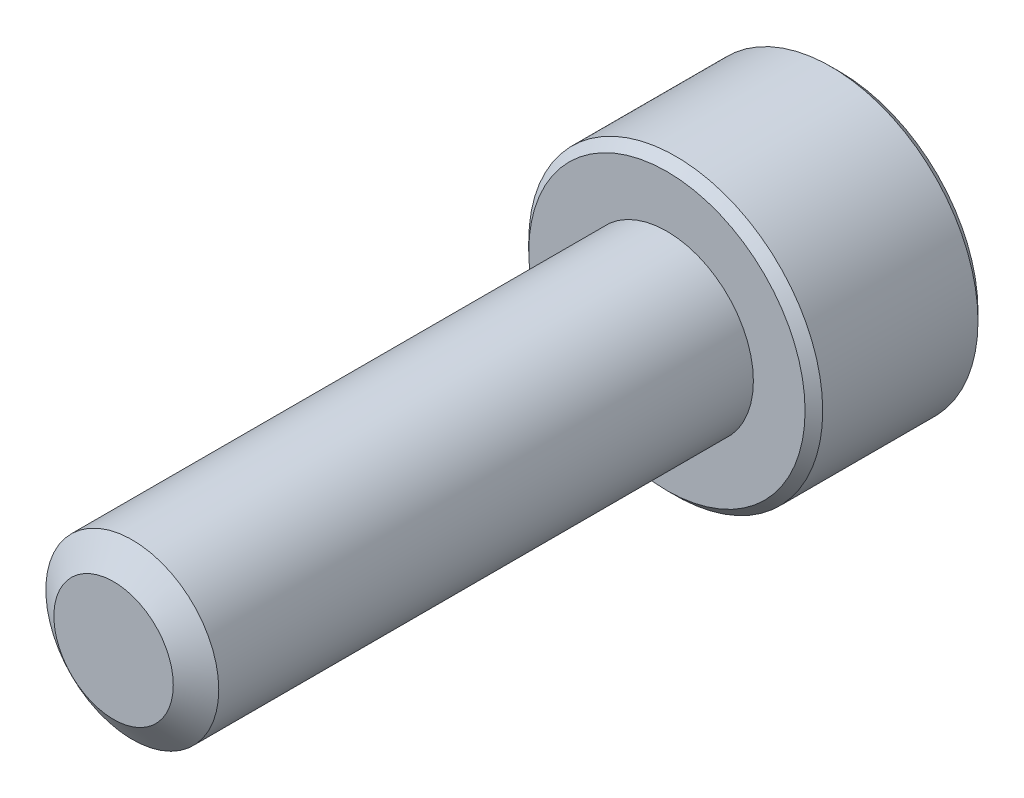
SolidWorks part; units mm, degrees
material "Alloy Steel"
ref_plane "Front Plane" through (0, 0, 0) normal (0, 0, 1) x (1, 0, 0)
ref_plane "Top Plane" through (0, 0, 0) normal (0, 1, 0) x (1, 0, 0)
ref_plane "Right Plane" through (0, 0, 0) normal (1, 0, 0) x (0, 0, -1)
sketch "Sketch1" plane through (0, 0, 0) normal (0, 0, 1) x (1, 0, 0)
  circle A0 centre (0, 0) radius 2.5
  dimension "OD" = 5
extrude "Extrude1" add sketch "Sketch1" against normal blind 16
sketch "Sketch2" plane through (0, 0, 0) normal (0, 0, 1) x (1, 0, 0)
  circle A0 centre (0, 0) radius 2.5 construction
  circle A1 centre (0, 0) radius 2.5
curve "Helix/Spiral1" [suppressed] pitch 0.8 height 16.8 turns 21 parameters "pitch"=0.8
sketch "Sketch3" plane through (0, 0, 0) normal (1, 0, 0) x (0, 0, -1)
  line L0 (-0.7, 2.5) -> (-0.4, 1.9804)
  line L1 (-0.4, 1.9804) -> (-0.3, 1.9804)
  line L2 (-0.3, 1.9804) -> (0, 2.5)
  line L3 (-0.7, 2.5) -> (0, 2.5)
  line L4 (-0.35, 2.5) -> (-0.35, 1.9804) construction
  line L5 (-0.55, 2.2402) -> (-0.15, 2.2402) construction
  line L6 (0, 2.5) -> (0, -2.5) construction
  line L7 (0, -2.5) -> (16, -2.5) construction
  point P11 (3.6, -2.5)
  dimension "D1" = 0.1
  dimension "D2" = 0.4
  dimension "D3" = 60
  dimension "D4" = 3.6
sweep "Cut-Sweep1" [suppressed] cut profiles "Sketch3" path "Helix/Spiral1"
sketch "Sketch4" plane through (0, 0, 0) normal (1, 0, 0) x (0, 0, -1)
  line L0 (0.5417, 2.5) -> (0, 1.7264)
  line L1 (0, 1.7264) -> (0, 2.5)
  line L2 (0.5417, 2.5) -> (0, 2.5)
  line L3 (-0.7, 2.5) -> (0, 2.5) construction
  line L4 (0, 0) -> (7.0209, 0) construction
  dimension "D1" = 55
  dimension "D2" = 0.254
revolve "Cut-Revolve1" cut sketch "Sketch4" angle 360 about L4
sketch "Sketch5" [suppressed] plane through (0, 0, 0) normal (1, 0, 0) x (0, 0, -1)
  line L0 (16, -1.991) -> (16, 1.7838) construction
  line L1 (16, 2.5) -> (0.1203, 2.5)
  line L2 (16, 2.5) -> (16, 0)
  line L3 (16, 0) -> (0.0001, 0)
  line L4 (0.0001, 2.1698) -> (0.0001, 0)
  line L5 (0.1203, 2.5) -> (0.0001, 2.1698)
  line L6 (0, 0) -> (9.9695, 0) construction
  point P3 (0.0001, 2.5)
  point P10 (0.0001, 2.5)
  dimension "D1" = 0.3302
  dimension "Thread min" = 0.0001
  dimension "D3" = 20
revolve "partially thread" [suppressed] add sketch "Sketch5" angle 360 about L6
sketch "Sketch6" plane through (0, 0, -16) normal (0, 0, -1) x (-1, 0, 0)
  circle A0 centre (0, 0) radius 4.25
  dimension "head dia" = 8.5
extrude "Extrude2" add sketch "Sketch6" along normal blind 5
sketch "Sketch7" plane through (0, 0, -21) normal (0, 0, -1) x (-1, 0, 0)
  line L1 (0, 2.3094) -> (-2, 1.1547)
  line L2 (-2, 1.1547) -> (-2, -1.1547)
  line L3 (-2, -1.1547) -> (0, -2.3094)
  line L4 (0, -2.3094) -> (2, -1.1547)
  line L5 (2, -1.1547) -> (2, 1.1547)
  line L6 (2, 1.1547) -> (0, 2.3094)
  circle A0 centre (0, 0) radius 2 construction
  dimension "hex dia" = 4
extrude "Cut-Extrude1" cut sketch "Sketch7" against normal blind 3
sketch "Sketch8" plane through (0, 0, -21) normal (0, 0, -1) x (-1, 0, 0)
  circle A0 centre (0, 0) radius 2.3094
extrude "Cut-Extrude2" cut sketch "Sketch8" against normal through all draft 45
chamfer "Chamfer1" distance 0.255 angle 45 2 edges at (-4.25, 0, -21) (-4.25, 0, -16)
sketch "Sketch9" plane through (0, 0, 0) normal (1, 0, 0) x (0, 0, -1)
  line L0 (0, 2.5) -> (0, -2.5) construction
  line L1 (4.4, 2.5) -> (4.4, -2.5) construction
  dimension "D1" = 4.4
sketch "Sketch10" plane through (0, 0, 0) normal (1, 0, 0) x (0, 0, -1)
  line L0 (16, 2.5) -> (16, 0)
  line L1 (16, 2.5) -> (15.8, 2.5)
  line L2 (15.8, 2.5) -> (14.7645, 0)
  line L3 (16, 0) -> (14.7645, 0)
  line L4 (16, 3.995) -> (16, -3.995) construction
  dimension "D1" = 22.5
  dimension "D2" = 0.2
revolve "Revolve1" add sketch "Sketch10" angle 360 about L3
equation "\"D3@Helix/Spiral1\" = \"screw length@Extrude1\"+\"pitch@Helix/Spiral1\""
equation "\"D1@Sketch3\" = \"pitch@Helix/Spiral1\"*.125"
equation "\"D2@Sketch3\" = \"pitch@Helix/Spiral1\"*.5"
equation "\"D1@Cut-Extrude1\" = \"hex dia@Sketch7\"*.75"
equation "\"D1@Chamfer1\" = \"head dia@Sketch6\"*.03"
equation "\"D1@Sketch9\" = \"pitch@Helix/Spiral1\"*5.5"
equation "\"D2@Sketch10\" = \"pitch@Helix/Spiral1\"*.25"
equation "\"D4@Sketch3\" = \"pitch@Helix/Spiral1\"*4.50"
